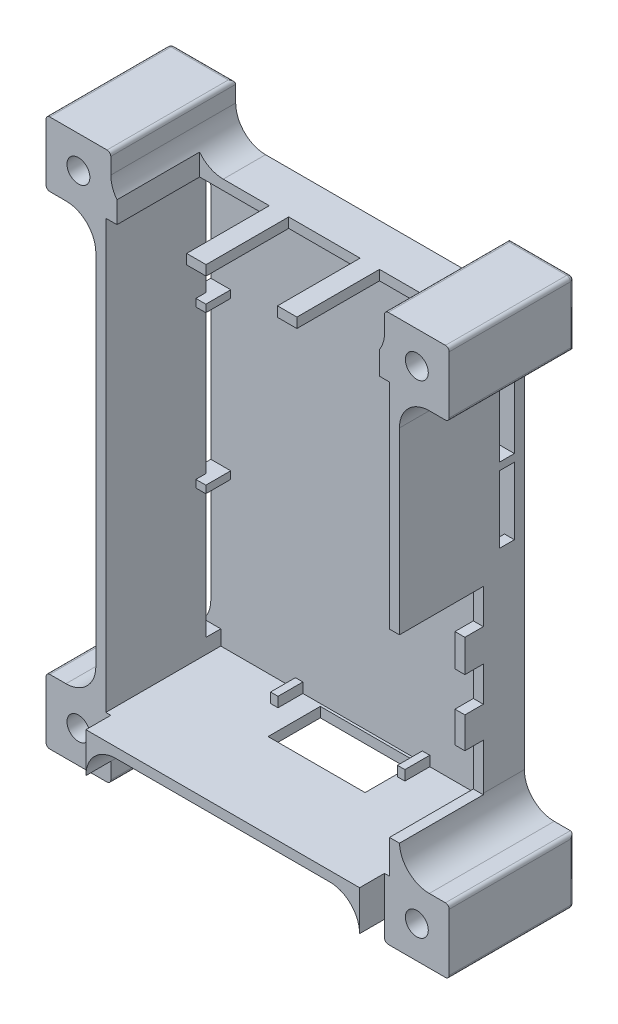
SolidWorks part; units mm, degrees
ref_plane "Front Plane" through (0, 0, 0) normal (0, 0, 1) x (1, 0, 0)
ref_plane "Top Plane" through (0, 0, 0) normal (0, 1, 0) x (1, 0, 0)
ref_plane "Right Plane" through (0, 0, 0) normal (1, 0, 0) x (0, 0, -1)
sketch "Sketch1" plane through (0, 0, 0) normal (0, 0, 1) x (1, 0, 0)
  line L1 (0, 0) -> (61, 0)
  line L2 (0, 0) -> (0, 90)
  line L3 (0, 90) -> (61, 90)
  line L4 (61, 0) -> (61, 90)
  dimension "D1" = 61
  dimension "D2" = 90
extrude "Boss-Extrude1" add sketch "Sketch1" along normal blind 2
sketch "Sketch2" plane through (0, 0, 2) normal (0, 0, 1) x (1, 0, 0)
  line L7 (0, -16.225) -> (0, 16.225) construction
  line L8 (0, 90) -> (0, 0)
  line L9 (2, 90) -> (2, 2)
  line L10 (2, 2) -> (59, 2)
  line L11 (59, 2) -> (59, 90)
  line L12 (2, 88) -> (2, 2)
  line L13 (2, 2) -> (59, 2)
  line L14 (59, 2) -> (59, 88)
  line L15 (0, 0) -> (61, 0)
  line L18 (61, 90) -> (61, 0)
  line L20 (2, 88) -> (59, 88)
  line L21 (0, 90) -> (61, 90)
  dimension "D1" = 2
extrude "Boss-Extrude2" add sketch "Sketch2" along normal blind 6.6
sketch "Sketch3" plane through (0, 0, 2) normal (0, 0, 1) x (1, 0, 0)
  line L0 (59, 2) -> (2, 2) construction
  line L1 (44, 2) -> (42.5, 2)
  line L2 (44, 2) -> (44, 4)
  line L3 (44, 4) -> (42.5, 4)
  line L4 (42.5, 2) -> (42.5, 4)
  line L5 (2, 2) -> (2, 88) construction
  line L6 (17, 2) -> (18.5, 2)
  line L7 (17, 2) -> (17, 4)
  line L8 (17, 4) -> (18.5, 4)
  line L9 (18.5, 2) -> (18.5, 4)
  line L10 (2, 32) -> (4, 32)
  line L11 (2, 32) -> (2, 33.5)
  line L12 (2, 33.5) -> (4, 33.5)
  line L13 (4, 32) -> (4, 33.5)
  line L14 (59, 88) -> (59, 2) construction
  line L15 (59, 32) -> (57, 32)
  line L16 (59, 32) -> (59, 33.5)
  line L17 (59, 33.5) -> (57, 33.5)
  line L18 (57, 32) -> (57, 33.5)
  line L19 (2, 2) -> (2, 88) construction
  line L20 (59, 63.5) -> (57, 63.5)
  line L21 (59, 63.5) -> (59, 65)
  line L22 (59, 65) -> (57, 65)
  line L23 (57, 63.5) -> (57, 65)
  line L24 (2, 63.5) -> (4, 63.5)
  line L25 (2, 63.5) -> (2, 65)
  line L26 (2, 65) -> (4, 65)
  line L27 (4, 63.5) -> (4, 65)
  line L28 (59, 2) -> (2, 2) construction
  dimension "D1" = 1.5
  dimension "D2" = 1.5
  dimension "D3" = 1.5
  dimension "D4" = 1.5
  dimension "D5" = 1.5
  dimension "D6" = 1.5
  dimension "D7" = 2
  dimension "D8" = 2
  dimension "D9" = 2
  dimension "D10" = 2
  dimension "D11" = 2
  dimension "D12" = 2
  dimension "D13" = 30
  dimension "D14" = 30
  dimension "D15" = 30
  dimension "D16" = 30
  dimension "D17" = 15
  dimension "D18" = 15
extrude "Boss-Extrude3" add sketch "Sketch3" along normal blind 5
sketch "Sketch4" plane through (0, 0, 8.6) normal (0, 0, 1) x (1, 0, 0)
  line L1 (61, 90) -> (0, 90)
  line L3 (59, 88) -> (2, 88)
  line L5 (61, 90) -> (61, 0)
  line L6 (0, 90) -> (0, 0)
  line L7 (0, 0) -> (61, 0)
  line L8 (2, 2) -> (59, 2)
  line L9 (2, 88) -> (2, 2)
  line L10 (59, 2) -> (59, 88)
  line L11 (59, 2) -> (59, 88) construction
extrude "Boss-Extrude4" add sketch "Sketch4" along normal blind 16.5
sketch "Sketch5" plane through (0, 90, 0) normal (0, 1, 0) x (1, 0, 0)
  line L1 (57, -8.5) -> (40.4, -8.5)
  line L3 (57, -22.25) -> (40.4, -22.25) construction
  line L4 (40.4, -8.5) -> (40.4, -22.25)
  line L5 (61, 0) -> (0, 0) construction
  line L6 (61, -25.1) -> (0, -25.1) construction
  line L7 (36.5, -25.1) -> (22.15, -25.1)
  line L8 (36.5, -25.1) -> (36.5, -8.5)
  line L9 (36.5, -8.5) -> (22.15, -8.5)
  line L10 (22.15, -25.1) -> (22.15, -8.5)
  line L11 (0, -25.1) -> (0, 0) construction
  line L12 (18.25, -25.1) -> (4.25, -25.1)
  line L13 (18.25, -25.1) -> (18.25, -8.5)
  line L14 (18.25, -8.5) -> (4.25, -8.5)
  line L15 (4.25, -25.1) -> (4.25, -8.5)
  line L17 (57, -25.1) -> (40.4, -25.1)
  line L19 (57, -22.25) -> (40.4, -22.25) construction
  line L20 (40.4, -25.1) -> (40.4, -22.25)
  line L21 (57, -8.5) -> (57, -25.1)
  line L22 (61, -25.1) -> (61, 0) construction
  point P21 (61, -12.55)
  dimension "D2" = 16.6
  dimension "D3" = 13.75
  dimension "D4" = 8.5
  dimension "D5" = 4.25
  dimension "D6" = 3.9
  dimension "D7" = 14
  dimension "D8" = 8.5
  dimension "D9" = 8.5
  dimension "D10" = 3.9
  dimension "D11" = 4
  dimension "D12" = 0
extrude "Cut-Extrude1" cut sketch "Sketch5" against normal blind 2
sketch "Sketch7" plane through (61, 0, 0) normal (1, 0, 0) x (0, 0, -1)
  line L0 (-11.95, 18.25) -> (-11.95, 24.5)
  line L8 (-11.95, 18.25) -> (-8.25, 18.25)
  line L9 (-8.25, 8.75) -> (-8.25, 18.25)
  line L10 (-11.95, 24.5) -> (-8.25, 24.5)
  line L12 (-11.95, 38) -> (-8.25, 38)
  line L14 (-11.95, 31.5) -> (-8.25, 31.5)
  line L18 (-25.1, 0) -> (-25.1, 90) construction
  line L19 (-25.1, 8.75) -> (-25.1, 45)
  line L21 (-11.95, 38) -> (-11.95, 31.5)
  line L22 (-8.25, 8.75) -> (-25.1, 8.75)
  line L23 (-25.1, 45) -> (-8.25, 45)
  line L24 (-25.1, 0) -> (0, 0) construction
  line L25 (-8.25, 24.5) -> (-8.25, 31.5)
  line L26 (-8.25, 38) -> (-8.25, 45)
  line L28 (0, 0) -> (0, 90) construction
  line L29 (0, 33.55) -> (0, -33.55) construction
  line L30 (-2, 85) -> (-5, 85)
  line L31 (-2, 85) -> (-2, 50)
  line L32 (-2, 50) -> (-5, 50)
  line L33 (-5, 85) -> (-5, 50)
  line L34 (-25.1, 90) -> (0, 90) construction
  point P0 (-8.25, 13.5)
  point P16 (-8.25, 41.5)
  point P18 (-10.1, 18.25)
  point P20 (-8.25, 28)
  dimension "D1" = 9.5
  dimension "D2" = 28
  dimension "D3" = 7
  dimension "D4" = 7
  dimension "D5" = 13.5
  dimension "D6" = 41.5
  dimension "D7" = 3.7
  dimension "D8" = 3.7
  dimension "D9" = 8.25
  dimension "D10" = 0
  dimension "D11" = 0
  dimension "D12" = 2
  dimension "D13" = 5
  dimension "D14" = 3
  dimension "D15" = 35
extrude "Cut-Extrude2" cut sketch "Sketch7" against normal blind 2
sketch "Sketch8" plane through (0, 0, 0) normal (0, -1, 0) x (-1, 0, 0)
  line L2 (-22.5, -13) -> (-22.5, -2.5)
  line L3 (-22.5, -2.5) -> (-42, -2.5)
  line L4 (-42, -13) -> (-42, -2.5)
  line L5 (0, 13.805) -> (0, -13.805) construction
  line L6 (-61, -25.1) -> (-61, 0) construction
  line L7 (-33.55, 0) -> (33.55, 0) construction
  line L8 (-22.5, -13) -> (-42, -13)
  dimension "D1" = 22.5
  dimension "D2" = 19
  dimension "D3" = 2.5
  dimension "D4" = 10.5
extrude "Cut-Extrude3" cut sketch "Sketch8" against normal blind 2
sketch "Sketch9" plane through (0, 0, 0) normal (-1, 0, 0) x (0, 0, 1)
  line L0 (0, -33.55) -> (0, 33.55) construction
  line L1 (5, 85) -> (2, 85)
  line L2 (5, 85) -> (5, 5)
  line L3 (5, 5) -> (2, 5)
  line L4 (2, 85) -> (2, 5)
  line L5 (25.1, 90) -> (0, 90) construction
  line L6 (13.805, 0) -> (-13.805, 0) construction
  dimension "D1" = 2
  dimension "D2" = 3
  dimension "D3" = 5
  dimension "D4" = 5
extrude "Cut-Extrude4" cut sketch "Sketch9" against normal blind 2
sketch "Sketch10" plane through (0, 0, 25.1) normal (0, 0, 1) x (1, 0, 0)
  line L0 (61, 0) -> (61, 8.75) construction
  line L1 (0, 0) -> (61, 0)
  line L2 (0, 0) -> (0, 2)
  line L3 (0, 2) -> (61, 2)
  line L4 (61, 0) -> (61, 2)
  dimension "D1" = 2
extrude "Boss-Extrude5" add sketch "Sketch10" along normal blind 5
sketch "Sketch12" plane through (2, 0, 0) normal (-1, 0, 0) x (0, 0, 1)
  line L0 (5, 63.5) -> (2, 63.5) construction
  line L1 (2, 65) -> (5, 65)
  line L2 (2, 65) -> (2, 63.5)
  line L3 (2, 63.5) -> (5, 63.5)
  line L4 (5, 65) -> (5, 63.5)
  line L5 (5, 32) -> (2, 32) construction
  line L6 (2, 33.5) -> (5, 33.5)
  line L7 (2, 33.5) -> (2, 32)
  line L8 (2, 32) -> (5, 32)
  line L9 (5, 33.5) -> (5, 32)
extrude "Boss-Extrude6" add sketch "Sketch12" along normal blind 2
sketch "Sketch13" plane through (59, 0, 0) normal (1, 0, 0) x (0, 0, -1)
  line L1 (-2, 63.5) -> (-5, 63.5)
  line L2 (-2, 63.5) -> (-2, 65)
  line L3 (-2, 65) -> (-5, 65)
  line L4 (-5, 63.5) -> (-5, 65)
extrude "Boss-Extrude7" add sketch "Sketch13" along normal blind 2
sketch "Sketch20" plane through (0, 0, 0) normal (0, 0, -1) x (-1, 0, 0)
  line L0 (-61, 90) -> (0, 90) construction
  line L1 (-3, 3) -> (10, 3)
  line L2 (-3, 3) -> (-3, -10)
  line L3 (-3, -10) -> (10, -10)
  line L4 (10, 3) -> (10, -10)
  line L5 (-3, 3) -> (10, -10) construction
  line L6 (-3, -10) -> (10, 3) construction
  line L7 (-58, 87) -> (-71, 87)
  line L8 (-58, 87) -> (-58, 100)
  line L9 (-58, 100) -> (-71, 100)
  line L10 (-71, 87) -> (-71, 100)
  line L11 (-58, 87) -> (-71, 100) construction
  line L12 (-58, 100) -> (-71, 87) construction
  line L13 (-61, 0) -> (-61, 90) construction
  line L14 (0, 0) -> (-61, 0) construction
  line L15 (0, 90) -> (0, 0) construction
  point P4 (3.5, -3.5)
  point P9 (-64.5, 93.5)
  dimension "D1" = 3
  dimension "D2" = 3
  dimension "D3" = 13
  dimension "D4" = 13
  dimension "D5" = 3
  dimension "D6" = 13
  dimension "D7" = 3
  dimension "D8" = 13
extrude "Boss-Extrude8" add sketch "Sketch20" against normal up to surface (25.1 mm away) up to face at (2.0833, 60, 25.1)
sketch "Sketch25" plane through (0, 0, 25.1) normal (0, 0, 1) x (1, 0, 0)
  line L1 (3, 3) -> (-10, 3)
  line L2 (3, 3) -> (3, -10)
  line L3 (3, -10) -> (-10, -10)
  line L4 (-10, 3) -> (-10, -10)
  line L5 (3, 3) -> (-10, -10) construction
  line L6 (3, -10) -> (-10, 3) construction
  line L7 (3, -10) -> (3.25, -10)
  line L8 (3, -10) -> (3, 3)
  line L9 (3, 3) -> (3.25, 3)
  line L10 (3.25, -10) -> (3.25, 3)
  line L11 (3, -10) -> (3.25, 3) construction
  line L12 (3, 3) -> (3.25, -10) construction
  point P4 (-3.5, -3.5)
  point P10 (3.125, -3.5)
  dimension "D1" = 0.25
extrude "Cut-Extrude11" cut sketch "Sketch25" along normal through all contours L2 L1 L4 L3 | L8 L7 L10 L9
sketch "Sketch26" plane through (0, 0, 25.1) normal (0, 0, 1) x (1, 0, 0)
  line L1 (3, 3) -> (2, 3)
  line L2 (3, 3) -> (3, 2)
  line L3 (3, 2) -> (2, 2)
  line L4 (2, 3) -> (2, 2)
  line L5 (3, 3) -> (2, 2) construction
  line L6 (3, 2) -> (2, 3) construction
  line L7 (58, 87) -> (59, 87)
  line L8 (58, 87) -> (58, 88)
  line L9 (58, 88) -> (59, 88)
  line L10 (59, 87) -> (59, 88)
  line L11 (58, 87) -> (59, 88) construction
  line L12 (58, 88) -> (59, 87) construction
  point P4 (2.5, 2.5)
  point P10 (58.5, 87.5)
  dimension "D1" = 1
  dimension "D2" = 1
  dimension "D3" = 1
  dimension "D4" = 1
extrude "Cut-Extrude12" cut sketch "Sketch26" against normal up to surface (23.1 mm away) up to face at (30.4, 40.25, 2)
sketch "Sketch27" plane through (0, 0, 25.1) normal (0, 0, 1) x (1, 0, 0)
  line L0 (64.5, 100) -> (64.5, 87) construction
  line L1 (58, 100) -> (71, 100) construction
  line L2 (71, 87) -> (61, 87) construction
  line L3 (71, 93.5) -> (58, 93.5) construction
  line L4 (71, 100) -> (71, 87) construction
  line L5 (58, 90) -> (58, 100) construction
  line L6 (-3.5, -10) -> (-3.5, 3) construction
  line L7 (3, -10) -> (-10, -10) construction
  line L8 (-10, 3) -> (0, 3) construction
  line L9 (-10, -3.5) -> (3, -3.5) construction
  line L10 (-10, -10) -> (-10, 3) construction
  line L11 (3, 0) -> (3, -10) construction
  circle A0 centre (-3.5, -3.5) radius 2.3
  circle A1 centre (64.5, 93.5) radius 2.3
  dimension "D1" = 4.6
  dimension "D2" = 4.6
extrude "Cut-Extrude13" cut sketch "Sketch27" against normal through all
sketch "Sketch31" plane through (0, 0, 0) normal (0, 0, -1) x (-1, 0, 0)
  line L0 (-71, 100) -> (-71, 87) construction
  line L1 (-61.8731, 88.95) -> (-59.2461, 93.5)
  line L2 (-59.2461, 93.5) -> (-61.8731, 98.05)
  line L3 (-61.8731, 98.05) -> (-67.1269, 98.05)
  line L4 (-67.1269, 98.05) -> (-69.7539, 93.5)
  line L5 (-69.7539, 93.5) -> (-67.1269, 88.95)
  line L6 (-67.1269, 88.95) -> (-61.8731, 88.95)
  line L7 (6.1269, -8.05) -> (8.7539, -3.5)
  line L8 (8.7539, -3.5) -> (6.1269, 1.05)
  line L9 (6.1269, 1.05) -> (0.8731, 1.05)
  line L10 (0.8731, 1.05) -> (-1.7539, -3.5)
  line L11 (-1.7539, -3.5) -> (0.8731, -8.05)
  line L12 (0.8731, -8.05) -> (6.1269, -8.05)
  line L13 (10, -10) -> (10, 3) construction
  circle A0 centre (-64.5, 93.5) radius 4.55 construction
  circle A1 centre (3.5, -3.5) radius 4.55 construction
  dimension "D1" = 9.1
  dimension "D2" = 9.1
  dimension "D3" = 30
  dimension "D4" = 30
extrude "Cut-Extrude17" cut sketch "Sketch31" against normal blind 6
fillet "Fillet3" radius 6 1 edges at (58, 90, 12.55) type face fillet first side face at (29.5687, 90, 15.7375) second side face at (58, 95, 12.55)
fillet "Fillet4" radius 6 1 edges at (61, 87, 12.55) type face fillet first side face at (61, 75, 3.5) second side face at (66, 87, 12.55)
sketch "Sketch33" plane through (0, 0, 25.1) normal (0, 0, 1) x (1, 0, 0)
  line L0 (2, 2) -> (3.25, 2) construction
  line L1 (3.25, 0) -> (3, 0)
  line L2 (3.25, 0) -> (3.25, 2)
  line L3 (3.25, 2) -> (3, 2)
  line L4 (3, 0) -> (3, 2)
  line L5 (3.25, 0) -> (3, 2) construction
  line L6 (3.25, 2) -> (3, 0) construction
  point P4 (3.125, 1)
  dimension "D1" = 0.25
extrude "Boss-Extrude10" add sketch "Sketch33" along normal up to surface (5 mm away) up to face at (32.125, 1, 30.1)
fillet "Fillet7" radius 6 1 edges at (3, 0, 12.55) type face fillet first side face at (3, -5, 12.55) second side face at (32.25, 0, 7.75)
fillet "Fillet8" radius 6 1 edges at (0, 3, 12.55) type face fillet first side face at (-5, 3, 12.55) second side face at (0, 48.5, 3.5)
sketch "Sketch34" plane through (0, 0, 25.1) normal (0, 0, 1) x (1, 0, 0)
  line L0 (18.25, 90) -> (4.25, 90) construction
  line L1 (59, 3) -> (71, 3)
  line L2 (58, 2) -> (58, -10)
  line L3 (58, -10) -> (71, -10)
  line L4 (71, 3) -> (71, -10)
  line L5 (59, 2) -> (71, -10) construction
  line L6 (58, -10) -> (71, 3) construction
  line L7 (2, 87) -> (-10, 87)
  line L8 (3, 88) -> (3, 100)
  line L9 (3, 100) -> (-10, 100)
  line L10 (-10, 87) -> (-10, 100)
  line L11 (2, 88) -> (-10, 100) construction
  line L12 (3, 100) -> (-10, 87) construction
  line L13 (0, 90) -> (0, 9) construction
  line L14 (61, 0) -> (61, 2) construction
  line L15 (9, 0) -> (61, 0) construction
  line L16 (59, 88) -> (2, 88) construction
  line L17 (2, 88) -> (2, 2) construction
  line L18 (3, 88) -> (2, 88)
  line L19 (2, 88) -> (2, 87)
  line L20 (59, 2) -> (59, 8.75) construction
  line L21 (44, 2) -> (59, 2) construction
  line L22 (59, 2) -> (59, 3)
  line L23 (58, 2) -> (59, 2)
  point P4 (64.5, -3.5)
  point P9 (-3.5, 93.5)
  dimension "D1" = 3
  dimension "D2" = 3
  dimension "D3" = 3
  dimension "D4" = 3
  dimension "D5" = 13
  dimension "D6" = 13
  dimension "D7" = 13
  dimension "D8" = 13
extrude "Boss-Extrude11" add sketch "Sketch34" against normal up to surface (25.1 mm away) up to face at (30.5, 45, 0)
sketch "Sketch35" plane through (0, 0, 25.1) normal (0, 0, 1) x (1, 0, 0)
  line L0 (-3.5, 100) -> (-3.5, 87) construction
  line L1 (3, 100) -> (-10, 100) construction
  line L2 (-10, 87) -> (0, 87) construction
  line L3 (-10, 93.5) -> (3, 93.5) construction
  line L4 (-10, 100) -> (-10, 87) construction
  line L5 (3, 90) -> (3, 100) construction
  line L6 (64.5, -10) -> (64.5, 3) construction
  line L7 (58, -10) -> (71, -10) construction
  line L8 (71, 3) -> (61, 3) construction
  line L9 (71, -3.5) -> (58, -3.5) construction
  line L10 (71, -10) -> (71, 3) construction
  line L11 (58, 0) -> (58, -10) construction
  circle A0 centre (-3.5, 93.5) radius 2.3
  circle A1 centre (64.5, -3.5) radius 2.3
  dimension "D1" = 4.6
  dimension "D2" = 4.6
extrude "Cut-Extrude18" cut sketch "Sketch35" against normal through all
fillet "Fillet9" radius 6 1 edges at (0, 87, 12.55) type face fillet first side face at (-5, 87, 12.55) second side face at (0, 48.5, 3.5)
fillet "Fillet10" radius 6 1 edges at (3, 90, 12.55) type face fillet first side face at (3, 95, 12.55) second side face at (25.2214, 90, 14.4)
fillet "Fillet11" radius 6 1 edges at (61, 3, 12.55) type face fillet first side face at (66, 3, 12.55) second side face at (61, 39.6, 10.585)
fillet "Fillet13" radius 0.75 20 edges at (71, -3.5, 0) (64.5, -10, 0) (-3.5, -10, 0) (-10, -3.5, 0) (-10, 93.5, 0) (-3.5, 100, 0) (71, 93.5, 0) (64.5, 100, 0) (71, 87, 12.55) (71, 100, 12.55) (58, 100, 12.55) (3, 100, 12.55) (-10, 100, 12.55) (-10, 87, 12.55) (-10, 3, 12.55) (-10, -10, 12.55) (3, -10, 12.55) (71, 3, 12.55) (58, -10, 12.55) (71, -10, 12.55)
sketch "Sketch36" plane through (0, 0, 0) normal (0, 0, -1) x (-1, 0, 0)
  line L0 (10, 99.25) -> (10, 87.75) construction
  line L1 (-59.2461, -3.5) -> (-61.8731, 1.05)
  line L2 (-61.8731, 1.05) -> (-67.1269, 1.05)
  line L3 (-67.1269, 1.05) -> (-69.7539, -3.5)
  line L4 (-69.7539, -3.5) -> (-67.1269, -8.05)
  line L5 (-67.1269, -8.05) -> (-61.8731, -8.05)
  line L6 (-61.8731, -8.05) -> (-59.2461, -3.5)
  line L7 (-1.7539, 93.5) -> (0.8731, 88.95)
  line L8 (0.8731, 88.95) -> (6.1269, 88.95)
  line L9 (6.1269, 88.95) -> (8.7539, 93.5)
  line L10 (8.7539, 93.5) -> (6.1269, 98.05)
  line L11 (6.1269, 98.05) -> (0.8731, 98.05)
  line L12 (0.8731, 98.05) -> (-1.7539, 93.5)
  line L15 (-70.25, 3) -> (-70.25, -9.25) construction
  circle A0 centre (-64.5, -3.5) radius 4.55 construction
  circle A1 centre (3.5, 93.5) radius 4.55 construction
  dimension "D1" = 30
  dimension "D2" = 30
  dimension "D3" = 9.1
  dimension "D4" = 9.1
extrude "Cut-Extrude19" cut sketch "Sketch36" against normal blind 6
sketch "Sketch38" plane through (0, 0, 25.1) normal (0, 0, 1) x (1, 0, 0)
  line L0 (61, 2) -> (3, 2) construction
  line L1 (69, -8) -> (58, -8)
  line L2 (69, -8) -> (69, 3)
  line L3 (69, 3) -> (58, 3)
  line L4 (58, -8) -> (58, 3)
  line L6 (61, 0) -> (61, 2) construction
  dimension "D1" = 11
  dimension "D2" = 8
  dimension "D3" = 1
extrude "Cut-Extrude20" cut sketch "Sketch38" along normal blind 10
fillet "Fillet14" radius 6 1 edges at (58, 0, 12.55) type face fillet first side face at (32.25, 0, 7.75) second side face at (58, -4.625, 12.55)
